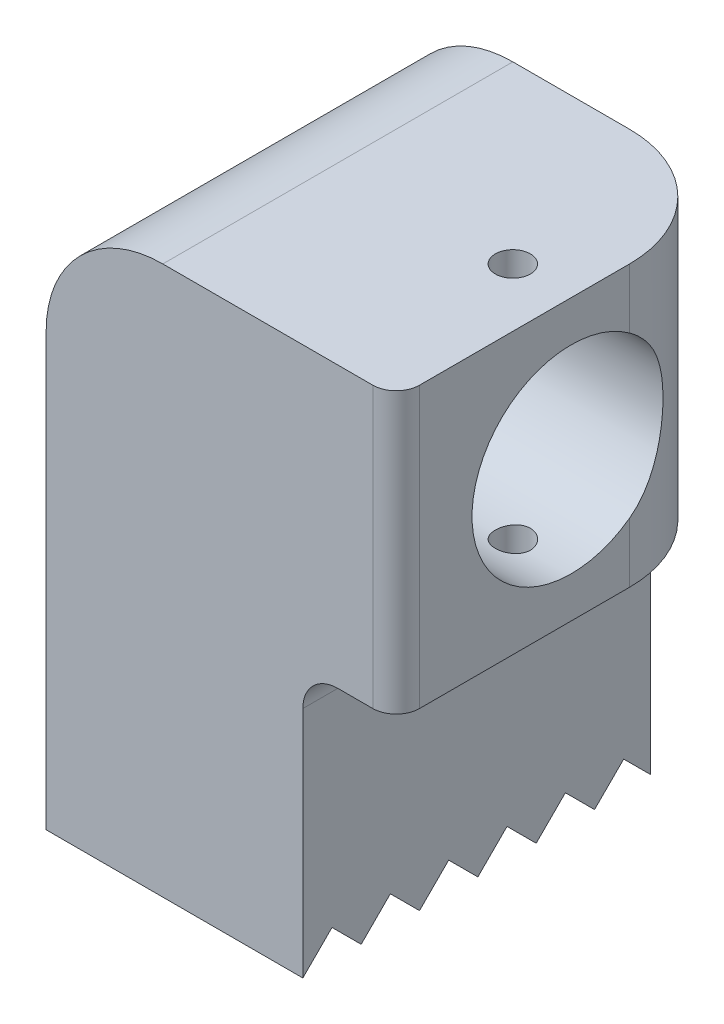
SolidWorks part; units mm, degrees
ref_plane "Alzado" through (0, 0, 0) normal (0, 0, 1) x (1, 0, 0)
ref_plane "Planta" through (0, 0, 0) normal (0, 1, 0) x (1, 0, 0)
ref_plane "Vista lateral" through (0, 0, 0) normal (1, 0, 0) x (0, 0, -1)
sketch "Croquis1" plane through (0, 0, 0) normal (0, 0, 1) x (1, 0, 0)
  line L1 (-15, -12) -> (15, -12)
  line L2 (-15, -12) -> (-15, 12)
  line L3 (-15, 12) -> (15, 12)
  line L4 (15, -12) -> (15, 12)
  line L5 (-15, -12) -> (15, 12) construction
  line L6 (-15, 12) -> (15, -12) construction
  line L7 (-15, -12) -> (7, -12)
  line L8 (-15, -12) -> (-15, -35)
  line L9 (-15, -35) -> (7, -35)
  line L10 (7, -12) -> (7, -35)
  point P0 (0, 0)
  dimension "D1" = 24
  dimension "D2" = 30
  dimension "D3" = 23
  dimension "D4" = 22
extrude "Saliente-Extruir1" add sketch "Croquis1" along normal mid plane 30 contours L1 L4 L3 L2 | L10 L1 L8 L9 region at (0, 0, 0) region at (-4, -23.5, 0)
sketch "Croquis2" plane through (15, 0, 0) normal (1, 0, 0) x (0, 0, -1)
  circle A0 centre (0, 0) radius 8.5
  dimension "D1" = 17
extrude "Cortar-Extruir1" cut sketch "Croquis2" against normal blind 25
fillet "Redondeo1" radius 10 1 edges at (-15, 12, 0)
fillet "Redondeo2" radius 10 1 edges at (15, 0, -15)
sketch "Croquis5" plane through (0, 12, 0) normal (0, 1, 0) x (1, 0, 0)
  line L0 (5, -15) -> (5, 15) construction
  line L1 (-17.9999, 0) -> (22.9471, 0) construction
  line L3 (15, -15) -> (15, 5) construction
  circle A1 centre (10, 0) radius 1.5
  dimension "D1" = 5
  dimension "D2" = 3
extrude "Cortar-Extruir3" cut sketch "Croquis5" against normal blind 30
fillet "Redondeo3" radius 2 1 edges at (15, 0, 15)
sketch "Croquis6" plane through (-15, 0, 0) normal (-1, 0, 0) x (0, 0, 1)
  line L0 (-15, -35) -> (-12.5, -32.5)
  line L1 (-12.5, -32.5) -> (-10, -35)
  line L2 (15, -35) -> (-15, -35) construction
  line L3 (-10, -35) -> (-15, -35)
  line L4 (-5, -35) -> (-10, -35)
  line L5 (-10, -35) -> (-7.5, -32.5)
  line L6 (-7.5, -32.5) -> (-5, -35)
  line L7 (0, -35) -> (-5, -35)
  line L8 (-5, -35) -> (-2.5, -32.5)
  line L9 (-2.5, -32.5) -> (0, -35)
  line L10 (5, -35) -> (0, -35)
  line L11 (0, -35) -> (2.5, -32.5)
  line L12 (2.5, -32.5) -> (5, -35)
  line L13 (10, -35) -> (5, -35)
  line L14 (5, -35) -> (7.5, -32.5)
  line L15 (7.5, -32.5) -> (10, -35)
  line L16 (15, -35) -> (10, -35)
  line L17 (10, -35) -> (12.5, -32.5)
  line L18 (12.5, -32.5) -> (15, -35)
  line L19 (-10, -35) -> (-5, -35) construction
  point P3 (-12.5, -35)
  dimension "D1" = 45
  dimension "D2" = 45
  dimension "D3" = 2.5
  dimension "D5" = 5
  dimension "D4" = 6
extrude "Cortar-Extruir4" cut sketch "Croquis6" against normal blind 25 contours L3 L0 L1 | L4 L5 L6 | L7 L8 L9 | L10 L11 L12 | L13 L14 L15 | L16 L17 L18
sketch "Croquis7" plane through (-15, 0, 0) normal (-1, 0, 0) x (0, 0, 1)
  line L0 (0, 10.4511) -> (0, -37.2771) construction
  line L1 (-15, -35) -> (15, -35) construction
  circle A0 centre (0, -14) radius 1.25
  circle A1 centre (0, -26) radius 1.25
  dimension "D1" = 2.5
  dimension "D2" = 12
  dimension "D3" = 9
extrude "Cortar-Extruir5" cut sketch "Croquis7" against normal blind 10
fillet "Redondeo4" radius 3 1 edges at (7, -12, 0.101)
